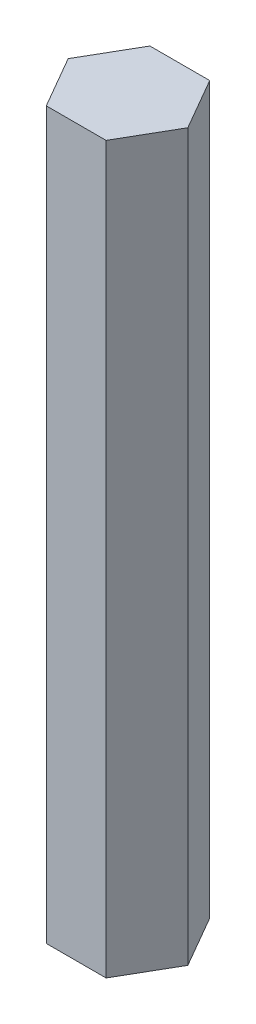
SolidWorks part; units mm, degrees
ref_plane "Front Plane" through (0, 0, 0) normal (0, 0, 1) x (1, 0, 0)
ref_plane "Top Plane" through (0, 0, 0) normal (0, 1, 0) x (1, 0, 0)
ref_plane "Right Plane" through (0, 0, 0) normal (1, 0, 0) x (0, 0, -1)
sketch "Sketch1" plane through (0, 0, 0) normal (0, 1, 0) x (1, 0, 0)
  line L1 (7.3323, 0) -> (3.6662, 6.35)
  line L2 (3.6662, 6.35) -> (-3.6662, 6.35)
  line L3 (-3.6662, 6.35) -> (-7.3323, 0)
  line L4 (-7.3323, 0) -> (-3.6662, -6.35)
  line L5 (-3.6662, -6.35) -> (3.6662, -6.35)
  line L6 (3.6662, -6.35) -> (7.3323, 0)
  circle A0 centre (0, 0) radius 6.35 construction
extrude "Boss-Extrude1" add sketch "Sketch1" along normal blind 88.9 contours L2 L3 L4 L5 L6 L1
ref_axis "Axis1" through (0, -8.255, 0) along (0, 1, 0)
